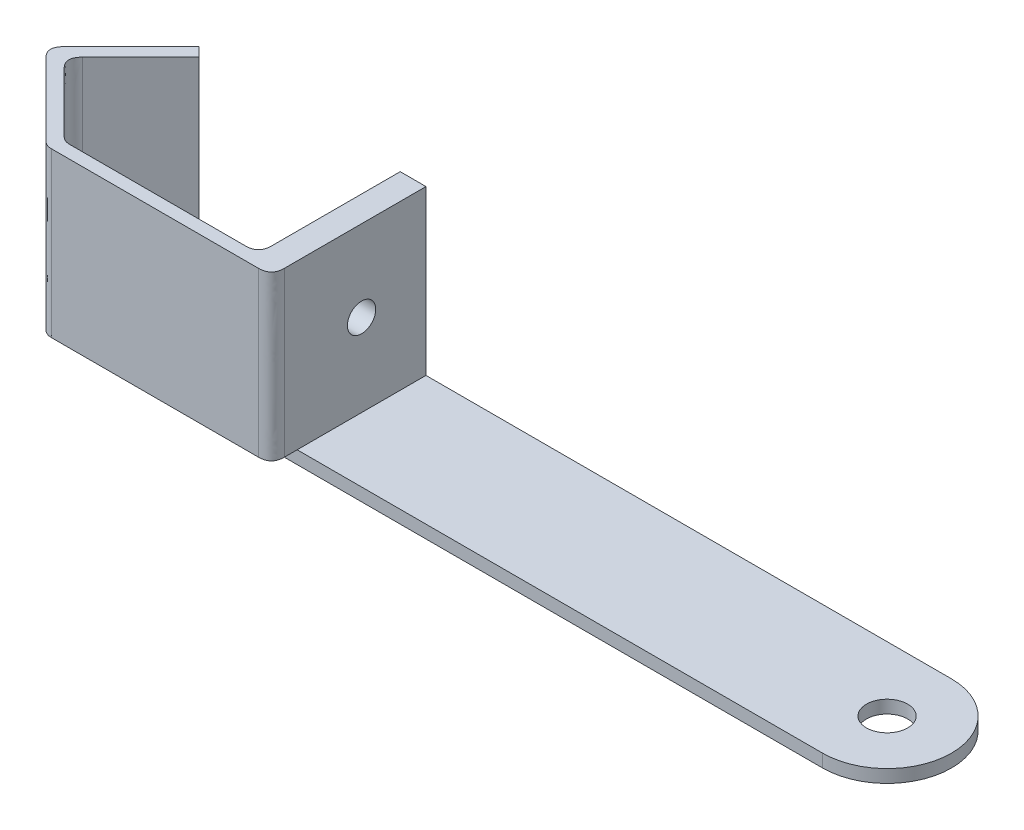
SolidWorks part; units mm, degrees
material "1060 Alloy"
ref_plane "Front" through (0, 0, 0) normal (0, 0, 1) x (1, 0, 0)
ref_plane "Top" through (0, 0, 0) normal (0, 1, 0) x (1, 0, 0)
ref_plane "Right" through (0, 0, 0) normal (1, 0, 0) x (0, 0, -1)
sketch "Sketch1" plane through (0, 0, 0) normal (0, 1, 0) x (1, 0, 0)
  line L1 (0, 0) -> (-108.712, 0)
  line L3 (0, -25.4) -> (-108.712, -25.4)
  line L4 (-108.712, 0) -> (-108.712, -25.4)
  arc A0 (0, -25.4) -> (0, 0) centre (0, -12.7) ccw
  circle A2 centre (0, -12.7) radius 4.064
  dimension "D1" = 108.712
  dimension "D2" = 25.4
extrude "Boss-Extrude1" add sketch "Sketch1" against normal blind 2.54
ref_plane "Plane1" through (-108.712, 0, 0) normal (1, 0, 0) x (0, 0, -1)
sketch "Sketch2" plane through (-108.712, 0, 0) normal (1, 0, 0) x (0, 0, -1)
  line L1 (0, 0) -> (-30.48, 0)
  line L2 (0, 0) -> (0, 32.258)
  line L3 (0, 32.258) -> (-30.48, 32.258)
  line L4 (-30.48, 0) -> (-30.48, 32.258)
  dimension "D1" = 30.48
  dimension "D2" = 32.258
extrude "Boss-Extrude2" add sketch "Sketch2" along normal blind 5.08
ref_plane "Plane2" through (0, 0, 30.48) normal (0, 0, 1) x (1, 0, 0)
sketch "Sketch3" plane through (0, 0, 30.48) normal (0, 0, 1) x (1, 0, 0)
  line L2 (-108.712, 0) -> (-108.712, 32.258)
  line L3 (-108.712, 32.258) -> (-150.622, 32.258)
  line L4 (-150.622, 0) -> (-150.622, 32.258)
  line L6 (-108.712, 0) -> (-150.622, 0)
  dimension "D1" = 41.91
  dimension "D2" = 32.258
extrude "Boss-Extrude3" add sketch "Sketch3" against normal blind 2.54
fillet "Fillet1" radius 2.54 2 edges at (-108.712, 16.129, 27.94) (-103.632, 16.129, 30.48) conic rho 0.5
sketch "Sketch4" plane through (0, 32.258, 0) normal (0, 1, 0) x (1, 0, 0)
  line L0 (-150.622, -27.94) -> (-148.082, -30.48)
  line L1 (-50, -30.48) -> (50, -30.48) construction
  line L2 (-150.622, -27.94) -> (-150.622, -30.48)
  line L3 (-150.622, -30.48) -> (-148.082, -30.48)
extrude "Cut-Extrude1" cut sketch "Sketch4" against normal through all
ref_plane "Plane3" through (-89.281, 0, 89.281) normal (-0.7071, 0, 0.7071) x (0.7071, 0, 0.7071)
sketch "Sketch5" plane through (-89.281, 0, 89.281) normal (-0.7071, 0, 0.7071) x (0.7071, 0, 0.7071)
  line L1 (-86.7493, 32.258) -> (-104.5293, 32.258)
  line L2 (-86.7493, 32.258) -> (-86.7493, 0)
  line L3 (-86.7493, 0) -> (-104.5293, 0)
  line L4 (-104.5293, 32.258) -> (-104.5293, 0)
  dimension "D1" = 17.78
  dimension "D2" = 32.258
extrude "Boss-Extrude4" add sketch "Sketch5" against normal blind 2.54 separate body
sketch "Sketch6" plane through (0, 32.258, 0) normal (0, 1, 0) x (1, 0, 0)
  line L0 (-150.622, -27.94) -> (-147.0299, -27.94)
  line L1 (-101.3078, -77.2542) -> (-77.2542, -101.3078) construction
  line L2 (-148.8259, -26.1439) -> (-150.622, -27.94) construction
  line L3 (-150.622, -27.94) -> (-148.8259, -26.1439)
  line L4 (-111.252, -27.94) -> (-150.622, -27.94) construction
  line L5 (-148.8259, -26.1439) -> (-147.0299, -27.94)
extrude "Boss-Extrude5" add sketch "Sketch6" against normal blind 32.258
fillet "Fillet2" radius 2.54 2 edges at (-147.0299, 16.129, 27.94) (-148.082, 16.129, 30.48) conic rho 0.5
sketch "Sketch7" plane through (0, 32.258, 0) normal (0, 1, 0) x (1, 0, 0)
  line L0 (-161.3983, -13.5716) -> (-161.3983, -17.1637)
  line L2 (-148.8259, -29.7361) -> (-163.1944, -15.3676) construction
  line L3 (-161.3983, -13.5716) -> (-163.1944, -15.3676)
  line L4 (-163.1944, -15.3676) -> (-161.3983, -17.1637)
  dimension "D1" = 45
ref_plane "Plane4" through (-73.9134, 0, -73.9134) normal (-0.7071, 0, -0.7071) x (-0.7071, 0, 0.7071)
sketch "Sketch9" plane through (-73.9134, 0, -73.9134) normal (-0.7071, 0, -0.7071) x (-0.7071, 0, 0.7071)
  line L7 (123.7224, 32.258) -> (123.7224, 0)
  line L8 (123.7224, 0) -> (104.9264, 0)
  line L9 (122.9785, 0) -> (98.4236, 0) construction
  line L10 (104.9264, 0) -> (104.9264, 32.258)
  line L11 (98.4236, 32.258) -> (122.9785, 32.258) construction
  line L12 (104.9264, 32.258) -> (123.7224, 32.258)
  dimension "D1" = 18.796
extrude "Boss-Extrude6" add sketch "Sketch9" along normal blind 2.54 separate body
sketch "Sketch10" plane through (0, 0, 0) normal (0, 1, 0) x (1, 0, 0)
  line L0 (-161.3983, -13.5716) -> (-163.1944, -11.7755)
  line L1 (-163.1944, -11.7755) -> (-164.9904, -13.5716)
  line L2 (-164.9904, -13.5716) -> (-163.1944, -15.3676)
  line L3 (-163.1944, -15.3676) -> (-161.3983, -13.5716)
extrude "Boss-Extrude7" add sketch "Sketch10" along normal blind 32.258
fillet "Fillet3" radius 2.54 2 edges at (-161.3983, 16.129, 13.5716) (-164.9904, 16.129, 13.5716) conic rho 0.5
hole_wizard "W (0.22) Diameter Hole1" positions "3DSketch4" profile "Sketch12" hole size "W" standard "ANSI Inch"
sketch3d "3DSketch4"
  line L0 (-103.632, 0, 0) -> (-103.632, 32.258, 0) construction
  line L1 (-103.632, 0, 25.4) -> (-103.632, 0, 0) construction
  point P0 (-103.632, 16.256, 12.7)
  dimension "D1" = 12.7
  dimension "D2" = 16.256
sketch "Sketch12" plane through (-103.632, 16.256, 12.7) normal (0, 1, 0) x (0, 0, -1)
  line L0 (0, 0) -> (0, 6.7588)
  line L1 (0, 6.7588) -> (2.794, 5.08)
  line L2 (2.794, 5.08) -> (2.794, 0)
  line L5 (2.794, 0) -> (0, 0)
  line L10 (0, 6.7588) -> (-2.794, 5.08) construction
  line L11 (0, -6.35) -> (0, 107.95) construction
  dimension "Hole Dia." = 5.588
  dimension "Hole Depth" = 5.08
  dimension "Drill Angle" = 118
